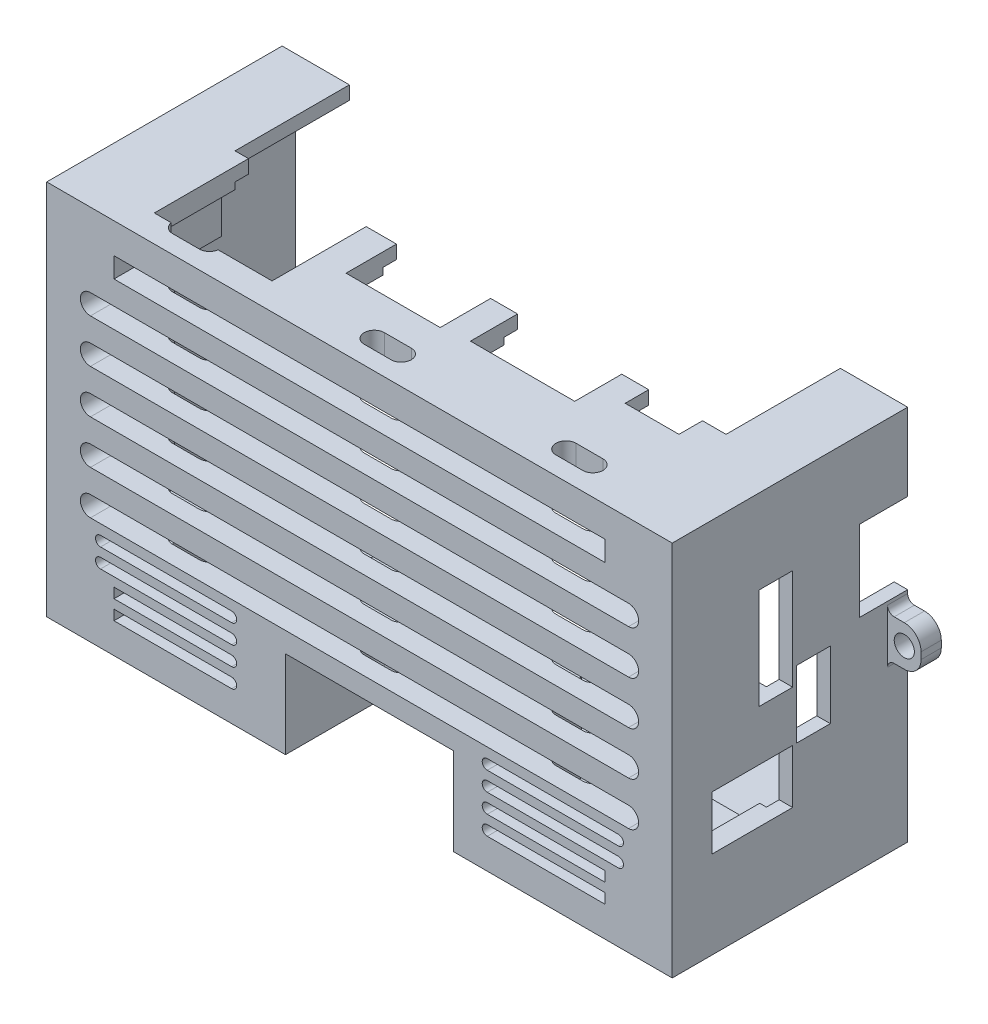
SolidWorks part; units mm, degrees
note: The reader was unsure of these and kept them because the rebuilt part matched: shared geometry of "草图3<3>", "草图3<5>", "草图3<7>".
ref_plane "前视基准面" through (0, 0, 0) normal (0, 0, 1) x (1, 0, 0)
ref_plane "上视基准面" through (0, 0, 0) normal (0, 1, 0) x (1, 0, 0)
ref_plane "右视基准面" through (0, 0, 0) normal (1, 0, 0) x (0, 0, -1)
sketch "草图1" plane through (0, 0, 0) normal (0, 0, 1) x (1, 0, 0)
  line L0 (-5, 0) -> (5, 0) construction
  line L1 (0, -5) -> (0, 5) construction
  line B0 (0, 28) -> (0, -28) construction
  line B1 (-46.5, 28) -> (46.5, 28)
  line B2 (-46.5, 28) -> (-46.5, -28)
  line B3 (-46.5, -28) -> (46.5, -28)
  line B4 (46.5, 28) -> (46.5, -28)
  line B5 (-46.5, 0) -> (46.5, 0) construction
  line B6 (-14.7618, 2.9185) -> (-17.7618, 2.9185) construction
  line B7 (0, 0) -> (-18, 0) construction
  line B8 (-14.0149, 5.8732) -> (-17.0149, 5.8732) construction
  line B9 (-12.6968, 8.8097) -> (-15.6968, 8.8097) construction
  line B10 (-10.6391, 11.7463) -> (-13.6391, 11.7463) construction
  line B11 (-7.4122, 14.6829) -> (-10.4122, 14.6829) construction
  line B12 (-15, 0) -> (-18, 0) construction
  line B13 (-20, 0) -> (20, 0) construction
  line B14 (-20, 20) -> (20, 20)
  line B15 (-20, 20) -> (-20, -20)
  line B16 (-20, -20) -> (20, -20)
  line B17 (20, 20) -> (20, -20)
  line B18 (0, 20) -> (0, -20) construction
  line B19 (-43.5, 25) -> (43.5, 25)
  line B20 (-43.5, 25) -> (-43.5, -25)
  line B21 (-43.5, -25) -> (43.5, -25)
  line B22 (43.5, 25) -> (43.5, -25)
  line B23 (-43.5, 0) -> (43.5, 0) construction
  line B24 (0, 25) -> (0, -25) construction
  line B25 (-39.5, 21) -> (-43.5, 21) construction
  line B26 (-39.5, 21) -> (-39.5, 25) construction
  line B27 (-39.5, -21) -> (39.5, -21) construction
  line B28 (39.5, -21) -> (39.5, 21) construction
  line B29 (39.5, 21) -> (43.5, 21) construction
  line B30 (39.5, 21) -> (39.5, 25) construction
  line B31 (-39.5, 21) -> (-39.5, -21) construction
  line B32 (39.5, 21) -> (-39.5, 21) construction
  line B33 (-39.5, -21) -> (-39.5, -25) construction
  line B34 (-39.5, -21) -> (-43.5, -21) construction
  line B35 (-23.25, 25) -> (-23.25, -25)
  line B36 (23.25, 25) -> (23.25, -25)
  line B37 (43.5, 17) -> (35.5, 17)
  line B38 (-43.5, 25) -> (-35.5, 25)
  line B39 (-43.5, 25) -> (-43.5, 17)
  line B40 (-43.5, 17) -> (-35.5, 17)
  line B41 (-35.5, 25) -> (-35.5, 17)
  line B42 (35.5, 25) -> (35.5, 17)
  line B43 (43.5, 25) -> (35.5, 25)
  line B44 (43.5, 25) -> (43.5, 17)
  line B45 (43.5, -25) -> (35.5, -25)
  line B46 (35.5, -25) -> (35.5, -17)
  line B47 (43.5, -17) -> (35.5, -17)
  line B48 (43.5, -25) -> (43.5, -17)
  line B49 (-43.5, -17) -> (-35.5, -17)
  line B50 (-35.5, -25) -> (-35.5, -17)
  line B51 (-43.5, -25) -> (-35.5, -25)
  line B52 (-43.5, -25) -> (-43.5, -17)
  line B53 (46.5, -18) -> (36.5, -18)
  line B54 (-46.5, -28) -> (-36.5, -28)
  line B55 (-46.5, -28) -> (-46.5, -18)
  line B56 (-46.5, -18) -> (-36.5, -18)
  line B57 (-36.5, -28) -> (-36.5, -18)
  line B58 (36.5, -28) -> (36.5, -18)
  line B59 (46.5, -28) -> (36.5, -28)
  line B60 (46.5, -28) -> (46.5, -18)
  line B61 (46.5, 28) -> (36.5, 28)
  line B62 (36.5, 28) -> (36.5, 18)
  line B63 (46.5, 18) -> (36.5, 18)
  line B64 (46.5, 28) -> (46.5, 18)
  line B65 (-46.5, 18) -> (-36.5, 18)
  line B66 (-36.5, 28) -> (-36.5, 18)
  line B67 (-46.5, 28) -> (-36.5, 28)
  line B68 (-46.5, 28) -> (-46.5, 18)
  circle B69 centre (0, 0) radius 18 construction
  circle B70 centre (-39.5, 21) radius 2
  circle B71 centre (39.5, 21) radius 2
  circle B72 centre (39.5, -21) radius 2
  circle B73 centre (-39.5, -21) radius 2
  circle B74 centre (0, 0) radius 18
  arc B75 (15, -1) -> (15, 1) centre (15, 0) ccw
  line B76 (-14.7618, 3.9185) -> (14.7618, 3.9185)
  line B77 (-12.6968, 9.8097) -> (12.6968, 9.8097)
  arc B78 (-10.6391, 12.7463) -> (-10.6391, 10.7463) centre (-10.6391, 11.7463) ccw
  line B79 (-10.6391, -12.7463) -> (10.6391, -12.7463)
  line B80 (-12.6968, -9.8097) -> (12.6968, -9.8097)
  line B81 (-12.6968, -7.8097) -> (12.6968, -7.8097)
  line B82 (-14.0149, -6.8732) -> (14.0149, -6.8732)
  line B83 (-14.0149, -4.8732) -> (14.0149, -4.8732)
  line B84 (-14.7594, -3.9185) -> (14.7642, -3.8479)
  line B85 (-14.7642, -1.9185) -> (14.7594, -1.8479)
  line B86 (-15, -1) -> (15, -1)
  line B87 (-15, 1) -> (15, 1)
  line B88 (-14.7618, 1.9185) -> (14.7618, 1.9185)
  line B89 (-14.0149, 4.8732) -> (14.0149, 4.8732)
  line B90 (-14.0149, 5.8732) -> (14.0149, 5.8732) construction
  line B91 (-14.7618, 2.9185) -> (14.7618, 2.9185) construction
  line B92 (-14.0149, 6.8732) -> (14.0149, 6.8732)
  line B93 (-12.6968, 8.8097) -> (12.6968, 8.8097) construction
  line B94 (-12.6968, 7.8097) -> (12.6968, 7.8097)
  line B95 (-10.6391, 11.7463) -> (10.6391, 11.7463) construction
  line B96 (-10.6391, 12.7463) -> (10.6391, 12.7463)
  line B97 (-10.6391, 10.7463) -> (10.6391, 10.7463)
  line B98 (-7.4122, 14.6829) -> (7.4122, 14.6829) construction
  line B99 (-7.4122, 15.6829) -> (7.4122, 15.6829)
  line B100 (-7.4122, 13.6829) -> (7.4122, 13.6829)
  line B101 (-14.7618, -2.9185) -> (14.7618, -2.8479) construction
  line B102 (-14.0149, -5.8732) -> (14.0149, -5.8732) construction
  line B103 (-12.6968, -8.8097) -> (12.6968, -8.8097) construction
  line B104 (-10.6391, -11.7463) -> (10.6391, -11.7463) construction
  line B105 (-10.6391, -10.7463) -> (10.6391, -10.7463)
  line B106 (-7.4122, -14.6829) -> (7.4122, -14.638) construction
  line B107 (-7.4091, -15.6829) -> (7.4152, -15.638)
  line B108 (-7.4152, -13.6829) -> (7.4091, -13.638)
  line B109 (-15, 0) -> (15, 0) construction
  arc B110 (-14.7618, 3.9185) -> (-14.7618, 1.9185) centre (-14.7618, 2.9185) ccw
  arc B111 (14.7618, 1.9185) -> (14.7618, 3.9185) centre (14.7618, 2.9185) ccw
  arc B112 (-14.0149, 6.8732) -> (-14.0149, 4.8732) centre (-14.0149, 5.8732) ccw
  arc B113 (14.0149, 4.8732) -> (14.0149, 6.8732) centre (14.0149, 5.8732) ccw
  arc B114 (-12.6968, 9.8097) -> (-12.6968, 7.8097) centre (-12.6968, 8.8097) ccw
  arc B115 (12.6968, 7.8097) -> (12.6968, 9.8097) centre (12.6968, 8.8097) ccw
  arc B116 (10.6391, 10.7463) -> (10.6391, 12.7463) centre (10.6391, 11.7463) ccw
  arc B117 (-7.4122, 15.6829) -> (-7.4122, 13.6829) centre (-7.4122, 14.6829) ccw
  arc B118 (7.4122, 13.6829) -> (7.4122, 15.6829) centre (7.4122, 14.6829) ccw
  arc B119 (-14.7594, -3.9185) -> (-14.7642, -1.9185) centre (-14.7618, -2.9185) cw
  arc B120 (14.7594, -1.8479) -> (14.7642, -3.8479) centre (14.7618, -2.8479) cw
  arc B121 (-14.0149, -6.8732) -> (-14.0149, -4.8732) centre (-14.0149, -5.8732) cw
  arc B122 (14.0149, -4.8732) -> (14.0149, -6.8732) centre (14.0149, -5.8732) cw
  arc B123 (-12.6968, -9.8097) -> (-12.6968, -7.8097) centre (-12.6968, -8.8097) cw
  arc B124 (12.6968, -7.8097) -> (12.6968, -9.8097) centre (12.6968, -8.8097) cw
  arc B125 (-10.6391, -12.7463) -> (-10.6391, -10.7463) centre (-10.6391, -11.7463) cw
  arc B126 (10.6391, -10.7463) -> (10.6391, -12.7463) centre (10.6391, -11.7463) cw
  arc B127 (-7.4091, -15.6829) -> (-7.4152, -13.6829) centre (-7.4122, -14.6829) cw
  arc B128 (7.4091, -13.638) -> (7.4152, -15.638) centre (7.4122, -14.638) cw
  arc B129 (-15, 1) -> (-15, -1) centre (-15, 0) ccw
  dimension "D1" = 10
  dimension "D2" = 10
sketch_block_instance "tx2_boxes_with_fan-1"
sketch_block "tx2_boxes_with_fan" parameters "D5"=36, "D7"=4, "D14"=36, "D1"=3, "D2"=3, "D3"=3, "D4"=2, "D6"=40, "D8"=79, "D9"=42, "D10"=50, "D11"=87, "D12"=4, "D13"=4, "D15"=23.25, "D16"=8, "D17"=8, "D18"=1, "D19"=1
extrude "凸台-拉伸1" add sketch "草图1" along normal blind 35 contours B65 B2 B56 B20 B39 | B3 B57 B21 B52 B56 B2 | B58 B3 B4 B53 B48 B45 | B4 B63 B44 B22 B53 | B3 B58 B21 B51 B57 | B66 B1 B2 B65 B20 B19 | B63 B4 B1 B62 B43 B22
sketch "草图2" plane through (0, 28, 0) normal (0, 1, 0) x (1, 0, 0)
  line L0 (0, -35) -> (0, 0) construction
  line L1 (-46.5, 0) -> (46.5, 0)
  line L2 (-46.5, 0) -> (-46.5, -35)
  line L3 (-46.5, -35) -> (46.5, -35)
  line L4 (46.5, 0) -> (46.5, -35)
  line L5 (-46.5, -17.5) -> (46.5, -17.5) construction
  line L6 (-46.5, -17) -> (46.5, -17)
  line L7 (-46.5, -15.5) -> (46.5, -15.5)
  line L9 (-34.5, -17) -> (-17, -17)
  line L10 (-34.5, -17) -> (-34.5, -31)
  line L11 (-34.5, -31) -> (-17, -31)
  line L12 (-17, -17) -> (-17, -31)
  line L14 (-12.5, -17) -> (1.5, -17)
  line L15 (-12.5, -17) -> (-12.5, -24.5)
  line L16 (-12.5, -24.5) -> (1.5, -24.5)
  line L17 (1.5, -17) -> (1.5, -24.5)
  line L19 (5.5, -17) -> (21, -17)
  line L20 (5.5, -17) -> (5.5, -24)
  line L21 (5.5, -24) -> (21, -24)
  line L22 (21, -17) -> (21, -24)
  line L24 (25, -17) -> (33, -17)
  line L25 (25, -17) -> (25, -20.5)
  line L26 (25, -20.5) -> (33, -20.5)
  line L27 (33, -17) -> (33, -20.5)
  line B0 (-43.5, -17) -> (43.5, -17)
  line B1 (-43.5, -15.5) -> (43.5, -15.5)
  line B2 (-34, -17) -> (-17.5, -17)
  line B3 (-34, -17) -> (-34, -30.5)
  line B4 (-34, -30.5) -> (-17.5, -30.5)
  line B5 (-17.5, -17) -> (-17.5, -30.5)
  line B6 (-12, -17) -> (1, -17)
  line B7 (-12, -17) -> (-12, -24)
  line B8 (-12, -24) -> (1, -24)
  line B9 (1, -17) -> (1, -24)
  line B10 (6, -17) -> (20.5, -17)
  line B11 (6, -17) -> (6, -23.5)
  line B12 (6, -23.5) -> (20.5, -23.5)
  line B13 (20.5, -17) -> (20.5, -23.5)
  line B14 (25.5, -17) -> (32.5, -17)
  line B15 (25.5, -17) -> (25.5, -20)
  line B16 (25.5, -20) -> (32.5, -20)
  line B17 (32.5, -17) -> (32.5, -20)
  line B18 (-43.5, -17) -> (43.5, -17)
  line B19 (-43.5, -17) -> (-43.5, -32.5)
  line B20 (-43.5, -32.5) -> (43.5, -32.5)
  line B21 (43.5, -17) -> (43.5, -32.5)
  line B22 (-43.5, -15.5) -> (-43.5, -17)
  line B23 (43.5, -15.5) -> (43.5, -17)
  line B24 (0, -17) -> (0, -32.5) construction
  line B25 (43.5, -24.75) -> (-43.5, -24.75) construction
  line M7 (36.5, -35) -> (46.5, -35)
  line M8 (46.5, -35) -> (46.5, 0)
  line M42 (36.5, 0) -> (36.5, -35)
  dimension "D1" = 35
  dimension "D2" = 93
  dimension "D3" = 17
  dimension "D4" = 1.5
  dimension "D5" = 18
  dimension "D6" = 0.5
  dimension "D7" = 0.5
  dimension "D8" = 0.5
  dimension "D9" = 0.5
  dimension "D10" = 0.5
  dimension "D11" = 0.5
  dimension "D12" = 0.5
  dimension "D13" = 0.5
  dimension "D14" = 0.5
  dimension "D15" = 0.5
  dimension "D16" = 0.5
  dimension "D17" = 0.5
sketch_block_instance "tx2_ethernet_usb_interface-1"
sketch_block "tx2_ethernet_usb_interface" parameters "D1"=16.5, "D2"=13.5, "D3"=5.5, "D4"=7, "D5"=13, "D6"=14.5, "D7"=6.5, "D8"=5, "D9"=7, "D10"=3, "D11"=5, "D12"=1.5, "D13"=15.5
sketch "草图3" plane through (0, 0, 35) normal (0, 0, 1) x (1, 0, 0)
  line L0 (1.5, -12) -> (1.5, -25) construction
  line L1 (-11, -15) -> (14, -15)
  line L2 (-11, -15) -> (-11, -25)
  line L3 (-11, -25) -> (14, -25)
  line L4 (14, -15) -> (14, -25)
  line L5 (-14, -12) -> (17, -12)
  line L6 (-14, -12) -> (-14, -25)
  line L7 (-14, -25) -> (17, -25)
  line L8 (17, -12) -> (17, -25)
  line L9 (-14, -25) -> (-14, -28)
  line L10 (-46.5, 28) -> (46.5, 28)
  line L11 (-46.5, 28) -> (-46.5, -28)
  line L12 (-46.5, -28) -> (46.5, -28)
  line L13 (46.5, 28) -> (46.5, -28)
  line L14 (17, -25) -> (17, -28)
  line L15 (-11, -25) -> (-11, -28)
  line L16 (0, 0) -> (-18, 0) construction
  line L17 (14, -25) -> (14, -28)
  line L21 (-15, 0) -> (-18, 0) construction
  line L22 (-20, 0) -> (20, 0) construction
  line L27 (0, 20) -> (0, -20) construction
  line L28 (-43.5, 25) -> (43.5, 25)
  line L29 (-43.5, 25) -> (-43.5, -25)
  line L30 (-43.5, -25) -> (43.5, -25)
  line L31 (43.5, 25) -> (43.5, -25)
  line L32 (-43.5, 0) -> (43.5, 0) construction
  line L33 (0, 25) -> (0, -25) construction
  line L34 (-39.5, 21) -> (-43.5, 21) construction
  line L35 (-39.5, 21) -> (-39.5, 25) construction
  line L36 (-39.5, -21) -> (39.5, -21) construction
  line L37 (39.5, -21) -> (39.5, 21) construction
  line L38 (39.5, 21) -> (43.5, 21) construction
  line L39 (39.5, 21) -> (39.5, 25) construction
  line L40 (-39.5, 21) -> (-39.5, -21) construction
  line L41 (39.5, 21) -> (-39.5, 21) construction
  line L42 (-39.5, -21) -> (-39.5, -25) construction
  line L43 (-39.5, -21) -> (-43.5, -21) construction
  line L45 (23.25, 25) -> (23.25, -25)
  line L46 (43.5, 17) -> (35.5, 17)
  line L47 (-43.5, 25) -> (-35.5, 25)
  line L48 (-43.5, 25) -> (-43.5, 17)
  line L49 (-43.5, 17) -> (-35.5, 17)
  line L50 (-35.5, 25) -> (-35.5, 17)
  line L51 (35.5, 25) -> (35.5, 17)
  line L52 (43.5, 25) -> (35.5, 25)
  line L53 (43.5, 25) -> (43.5, 17)
  line L54 (43.5, -25) -> (35.5, -25)
  line L55 (35.5, -25) -> (35.5, -17)
  line L56 (43.5, -17) -> (35.5, -17)
  line L57 (43.5, -25) -> (43.5, -17)
  line L58 (-43.5, -17) -> (-35.5, -17)
  line L59 (-35.5, -25) -> (-35.5, -17)
  line L60 (-43.5, -25) -> (-35.5, -25)
  line L61 (-43.5, -25) -> (-43.5, -17)
  line L62 (46.5, -18) -> (36.5, -18)
  line L63 (-46.5, -28) -> (-36.5, -28)
  line L64 (-46.5, -28) -> (-46.5, -18)
  line L65 (-46.5, -18) -> (-36.5, -18)
  line L66 (-36.5, -28) -> (-36.5, -18)
  line L67 (36.5, -28) -> (36.5, -18)
  line L68 (46.5, -28) -> (36.5, -28)
  line L69 (46.5, -28) -> (46.5, -18)
  line L70 (46.5, 28) -> (36.5, 28)
  line L71 (36.5, 28) -> (36.5, 18)
  line L72 (46.5, 18) -> (36.5, 18)
  line L73 (46.5, 28) -> (46.5, 18)
  line L74 (-46.5, 18) -> (-36.5, 18)
  line L75 (-36.5, 28) -> (-36.5, 18)
  line L76 (-46.5, 28) -> (-36.5, 28)
  line L77 (-46.5, 28) -> (-46.5, 18)
  circle A1 centre (-39.5, 21) radius 2
  circle A2 centre (39.5, 21) radius 2
  circle A3 centre (39.5, -21) radius 2
  circle A4 centre (-39.5, -21) radius 2
  line B0 (-39, 16) -> (-39, 15.5)
  line B1 (-41.5, 16) -> (-41, 16)
  line B2 (-41.5, 16) -> (-41.5, 15.5)
  line B3 (-41.5, 15.5) -> (-41, 15.5)
  line B4 (-41, 16) -> (-41, 15.5)
  line B5 (-43.5, 25) -> (43.5, 25)
  line B6 (-43.5, 25) -> (-43.5, -25)
  line B7 (-43.5, -25) -> (43.5, -25)
  line B8 (43.5, 25) -> (43.5, -25)
  line B9 (-39, 16) -> (-38.5, 16)
  line B10 (-38.5, 16) -> (-38.5, 15.5)
  line B11 (-39, 15.5) -> (-38.5, 15.5)
  line B12 (-41.5, 13.5) -> (-41.5, 13)
  line B13 (-41.5, 13.5) -> (-41, 13.5)
  line B14 (-41, 13.5) -> (-41, 13)
  line B15 (-41.5, 13) -> (-41, 13)
  line B16 (-39, 13.5) -> (-39, 13)
  line B17 (-39, 13.5) -> (-38.5, 13.5)
  line B18 (-38.5, 13.5) -> (-38.5, 13)
  line B19 (-39, 13) -> (-38.5, 13)
  line B20 (-41.5, 11) -> (-41.5, 10.5)
  line B21 (-41.5, 11) -> (-41, 11)
  line B22 (-41, 11) -> (-41, 10.5)
  line B23 (-41.5, 10.5) -> (-41, 10.5)
  line B24 (-39, 11) -> (-39, 10.5)
  line B25 (-39, 11) -> (-38.5, 11)
  line B26 (-38.5, 11) -> (-38.5, 10.5)
  line B27 (-39, 10.5) -> (-38.5, 10.5)
  line B28 (-41.5, 8.5) -> (-41.5, 8)
  line B29 (-41.5, 8.5) -> (-41, 8.5)
  line B30 (-41, 8.5) -> (-41, 8)
  line B31 (-41.5, 8) -> (-41, 8)
  line B32 (-39, 8.5) -> (-39, 8)
  line B33 (-39, 8.5) -> (-38.5, 8.5)
  line B34 (-38.5, 8.5) -> (-38.5, 8)
  line B35 (-39, 8) -> (-38.5, 8)
  line B36 (-41.5, 6) -> (-41.5, 5.5)
  line B37 (-41.5, 6) -> (-41, 6)
  line B38 (-41, 6) -> (-41, 5.5)
  line B39 (-41.5, 5.5) -> (-41, 5.5)
  line B40 (-39, 6) -> (-39, 5.5)
  line B41 (-39, 6) -> (-38.5, 6)
  line B42 (-38.5, 6) -> (-38.5, 5.5)
  line B43 (-39, 5.5) -> (-38.5, 5.5)
  line B44 (-41.5, 3.5) -> (-41.5, 3)
  line B45 (-41.5, 3.5) -> (-41, 3.5)
  line B46 (-41, 3.5) -> (-41, 3)
  line B47 (-41.5, 3) -> (-41, 3)
  line B48 (-39, 3.5) -> (-39, 3)
  line B49 (-39, 3.5) -> (-38.5, 3.5)
  line B50 (-38.5, 3.5) -> (-38.5, 3)
  line B51 (-39, 3) -> (-38.5, 3)
  line B52 (-41.5, 1) -> (-41.5, 0.5)
  line B53 (-41.5, 1) -> (-41, 1)
  line B54 (-41, 1) -> (-41, 0.5)
  line B55 (-41.5, 0.5) -> (-41, 0.5)
  line B56 (-39, 1) -> (-39, 0.5)
  line B57 (-39, 1) -> (-38.5, 1)
  line B58 (-38.5, 1) -> (-38.5, 0.5)
  line B59 (-39, 0.5) -> (-38.5, 0.5)
  line B60 (-41.5, -1.5) -> (-41.5, -2)
  line B61 (-41.5, -1.5) -> (-41, -1.5)
  line B62 (-41, -1.5) -> (-41, -2)
  line B63 (-41.5, -2) -> (-41, -2)
  line B64 (-39, -1.5) -> (-39, -2)
  line B65 (-39, -1.5) -> (-38.5, -1.5)
  line B66 (-38.5, -1.5) -> (-38.5, -2)
  line B67 (-39, -2) -> (-38.5, -2)
  line B68 (-41.5, -4) -> (-41.5, -4.5)
  line B69 (-41.5, -4) -> (-41, -4)
  line B70 (-41, -4) -> (-41, -4.5)
  line B71 (-41.5, -4.5) -> (-41, -4.5)
  line B72 (-39, -4) -> (-39, -4.5)
  line B73 (-39, -4) -> (-38.5, -4)
  line B74 (-38.5, -4) -> (-38.5, -4.5)
  line B75 (-39, -4.5) -> (-38.5, -4.5)
  line B76 (-41.5, -6.5) -> (-41.5, -7)
  line B77 (-41.5, -6.5) -> (-41, -6.5)
  line B78 (-41, -6.5) -> (-41, -7)
  line B79 (-41.5, -7) -> (-41, -7)
  line B80 (-39, -6.5) -> (-39, -7)
  line B81 (-39, -6.5) -> (-38.5, -6.5)
  line B82 (-38.5, -6.5) -> (-38.5, -7)
  line B83 (-39, -7) -> (-38.5, -7)
  line B84 (0, 25) -> (0, -25) construction
  line B85 (28.5, 15) -> (43.5, 15)
  line B86 (28.5, 15) -> (28.5, 1)
  line B87 (28.5, 1) -> (43.5, 1)
  line B88 (43.5, 15) -> (43.5, 1)
  line B89 (36, -7.5) -> (43.5, -7.5)
  line B90 (36, -7.5) -> (36, -14.5)
  line B91 (36, -14.5) -> (43.5, -14.5)
  line B92 (43.5, -7.5) -> (43.5, -14.5)
  line B93 (-43.5, 0) -> (43.5, 0) construction
  line B94 (-7.5, -22.25) -> (-5.5, -22.25) construction
  line B95 (-7.5, -21.5) -> (-5.5, -21.5)
  line B96 (-7.5, -23) -> (-5.5, -23)
  arc B97 (-7.5, -21.5) -> (-7.5, -23) centre (-7.5, -22.25) ccw
  arc B98 (-5.5, -23) -> (-5.5, -21.5) centre (-5.5, -22.25) ccw
  line B99 (1.5, -21) -> (1.5, -23.5) construction
  line B100 (-0.5, -21) -> (3.5, -21)
  line B101 (-0.5, -21) -> (-0.5, -23.5)
  line B102 (-0.5, -23.5) -> (3.5, -23.5)
  line B103 (3.5, -21) -> (3.5, -23.5)
  line B104 (-0.5, -22.25) -> (3.5, -22.25) construction
  line B105 (0.5, -22.25) -> (2.5, -22.25) construction
  line B106 (0.5, -21.5) -> (2.5, -21.5)
  line B107 (0.5, -23) -> (2.5, -23)
  arc B108 (0.5, -21.5) -> (0.5, -23) centre (0.5, -22.25) ccw
  arc B109 (2.5, -23) -> (2.5, -21.5) centre (2.5, -22.25) ccw
  line B110 (9.5, -21) -> (9.5, -23.5) construction
  line B111 (7.5, -21) -> (11.5, -21)
  line B112 (7.5, -21) -> (7.5, -23.5)
  line B113 (7.5, -23.5) -> (11.5, -23.5)
  line B114 (11.5, -21) -> (11.5, -23.5)
  line B115 (7.5, -22.25) -> (11.5, -22.25) construction
  line B116 (8.5, -22.25) -> (10.5, -22.25) construction
  line B117 (8.5, -21.5) -> (10.5, -21.5)
  line B118 (8.5, -23) -> (10.5, -23)
  arc B119 (8.5, -21.5) -> (8.5, -23) centre (8.5, -22.25) ccw
  arc B120 (10.5, -23) -> (10.5, -21.5) centre (10.5, -22.25) ccw
  line B121 (-6.5, -21) -> (-6.5, -23.5) construction
  line B122 (-8.5, -21) -> (-4.5, -21)
  line B123 (-8.5, -21) -> (-8.5, -23.5)
  line B124 (-8.5, -23.5) -> (-4.5, -23.5)
  line B125 (-4.5, -21) -> (-4.5, -23.5)
  line B126 (-8.5, -22.25) -> (-4.5, -22.25) construction
  line B127 (-7.5, -22.25) -> (-5.5, -22.25) construction
  line B128 (-7.5, -21.5) -> (-5.5, -21.5)
  line B129 (-7.5, -23) -> (-5.5, -23)
  arc B130 (-7.5, -21.5) -> (-7.5, -23) centre (-7.5, -22.25) ccw
  arc B131 (-5.5, -23) -> (-5.5, -21.5) centre (-5.5, -22.25) ccw
  line M4 (43.5, 25) -> (43.5, -25)
  line M5 (43.5, -25) -> (-43.5, -25)
  line M6 (-43.5, -25) -> (-43.5, 25)
  line M7 (36.5, 25) -> (43.5, 25)
  line M8 (-46.5, -28) -> (46.5, -28)
  line M9 (46.5, -28) -> (46.5, 28)
  line M10 (46.5, 28) -> (36.5, 28)
  line M11 (-46.5, 28) -> (-46.5, -28)
  line M272 (-46.5, -28) -> (46.5, -28)
  line M274 (43.5, -25) -> (-43.5, -25)
  line M275 (-43.5, 25) -> (-36.5, 25)
  line M276 (-36.5, 25) -> (-36.5, 28)
  line M277 (-36.5, 28) -> (-46.5, 28)
  dimension "D11" = 4
  dimension "D1" = 3
  dimension "D2" = 3
  dimension "D3" = 25
  dimension "D4" = 10
  dimension "D5" = 3
  dimension "D6" = 3
  dimension "D12" = 79
  dimension "D13" = 42
  dimension "D14" = 50
  dimension "D15" = 87
  dimension "D16" = 4
  dimension "D17" = 4
  dimension "D20" = 8
  dimension "D21" = 8
  dimension "D22" = 1
  dimension "D23" = 1
sketch_block_instance "tx2_key_and_sd_card-3"
sketch_block "tx2_key_and_sd_card" parameters "D1"=0.5, "D2"=0.5, "D3"=2, "D4"=9, "D5"=2.5, "D6"=2.5, "D7"=15, "D8"=14, "D9"=10, "D10"=7.5, "D11"=7, "D12"=10.5, "D13"=87, "D14"=50
sketch_block_instance "button-8"
sketch_block "button" parameters "D1"=4, "D2"=2.5
sketch_block_instance "button-9"
sketch_block_instance "button-1"
extrude "切除-拉伸1" cut sketch "草图3" against normal blind 18 contours L75 L74 L48 M10 M11 M7 | L75 L48 L74 A1 M7 | L47 L75 L74 L29 L49 L50 | A1 | L66 L60 L65 L11 M8 M6 | L60 L66 L65 A4 M6 | A4 | L66 L59 L58 L61 L65 M5 | L67 L57 L62 A3 M5 | L54 L67 L62 L56 L55 M4 | L67 L62 L57 M8 M9 M5 | L72 L71 L52 M9 M10 M4 | L72 L52 L71 A2 M4 | A2 | L53 L72 L71 L28 L51 L46 | L10 L75 L47 L28 L71 M7
extrude "凸台-拉伸2" add sketch "草图3<3>" against normal blind 18 contours L75 L48 L74 A1 M275 | L60 L66 L65 A4 M6 | L67 L57 L62 A3 M274 | L72 L71 A2 M4 M7 | L66 L60 L65 L11 M272 M6 | L67 L62 L57 M272 M9 M274 | L13 L72 L53 L31 B8 L62 M4 | L74 L48 M11 M275 M276 M277 | L8 L5 L6 L2 L1 L4 M274
sketch "草图3<3>" plane through (0, 0, 35) normal (0, 0, 1) x (1, 0, 0) same geometry as "草图3"
extrude "凸台-拉伸3" add sketch "草图2" against normal blind 3 contours B20 B19 L6 L2 L3 M42 | B19 B20 L6 L27 L26 L25 L22 L21 L20 L17 L16 L15 L12 L11 L10 M42 | L6 B21 B20 M42 M7 M8 | B21 L6 B20 M42 | B23 L7 L6 M42 | L7 B23 L6 L4 | B22 L7 L2 L6
sketch "草图4" plane through (46.5, 0, 0) normal (1, 0, 0) x (0, 0, -1)
  line L0 (-35, 0) -> (0, 0) construction
  line L1 (-35, 28) -> (0, 28)
  line L2 (-35, 28) -> (-35, -28)
  line L3 (-35, -28) -> (0, -28)
  line L4 (0, 28) -> (0, -28)
  line L5 (-17.5, 28) -> (-17.5, -28) construction
  line L6 (-17, 28) -> (-17, -28)
  line L7 (-15.5, 28) -> (-15.5, -28)
  line L8 (-17.1, 8) -> (-22.1, 8) construction
  line L9 (-17.1, 15.5) -> (-22.1, 15.5)
  line L10 (-17.1, 15.5) -> (-17.1, 0.5)
  line L11 (-17.1, 0.5) -> (-22.1, 0.5)
  line L12 (-22.1, 15.5) -> (-22.1, 0.5)
  line L13 (-17.1, -11) -> (-29.1, -11) construction
  line L14 (-17.1, -7) -> (-29.1, -7)
  line L15 (-17.1, -7) -> (-17.1, -15)
  line L16 (-17.1, -15) -> (-29.1, -15)
  line L17 (-29.1, -7) -> (-29.1, -15)
  line L18 (-11.5, -2) -> (-16.5, -2) construction
  line L19 (-11.5, 3) -> (-16.5, 3)
  line L20 (-11.5, 3) -> (-11.5, -7)
  line L21 (-11.5, -7) -> (-16.5, -7)
  line L22 (-16.5, 3) -> (-16.5, -7)
  line L23 (0, 25) -> (-35, 25)
  line L24 (0, -25) -> (-35, -25)
  line L26 (-7.1806, 16.5) -> (0, 16.5)
  line L27 (-7.1806, 16.5) -> (-7.1806, 4.5)
  line L28 (-7.1806, 4.5) -> (0, 4.5)
  line L29 (0, 16.5) -> (0, 4.5)
  dimension "D1" = 17
  dimension "D2" = 1.5
  dimension "D3" = 15
  dimension "D4" = 5
  dimension "D5" = 8
  dimension "D6" = 12
  dimension "D7" = 14
  dimension "D8" = 17
  dimension "D9" = 0.1
  dimension "D10" = 0.1
  dimension "D11" = 10
  dimension "D12" = 5
  dimension "D13" = 27
  dimension "D14" = 1
  dimension "D15" = 25
  dimension "D16" = 25
  dimension "D17" = 12
  dimension "D18" = 1
extrude "切除-拉伸2" cut sketch "草图4" against normal blind 3 contours L9 L12 L11 L10 | L21 L20 L19 L7 | L14 L17 L16 L15 | L19 L22 L21 L7 | L27 L26 L29 L28
extrude "切除-拉伸3" cut sketch "草图3<5>" along normal blind 2 from surface at -18 contours L75 L48 L74 A1 M275 | L60 L66 L65 A4 M6 | L67 L57 L62 A3 M274 | L72 L71 A2 M4 M7 starting at face at (-40, -21.5, 17)
sketch "草图3<5>" plane through (0, 0, 35) normal (0, 0, 1) x (1, 0, 0) same geometry as "草图3"
sketch "草图5" plane through (0, 0, 35) normal (0, 0, 1) x (1, 0, 0)
  line L1 (-46.5, 28) -> (46.5, 28)
  line L2 (-46.5, 28) -> (-46.5, -28)
  line L3 (-46.5, -28) -> (46.5, -28)
  line L4 (46.5, 28) -> (46.5, -28)
extrude "凸台-拉伸4" add sketch "草图5" against normal blind 3
extrude "切除-拉伸4" cut sketch "草图3<7>" against normal blind 18 contours L17 L15 L12 M274 | L4 L1 L2 B111 B114 B113 B112 B100 B103 B102 B101 B122 B125 B124 B123 M274 | B125 B122 B123 B124 B98 B96 B97 B95 | B96 B98 B95 B97 | B103 B100 B101 B102 B109 B107 B108 B106 | B107 B109 B106 B108 | B114 B111 B112 B113 B120 B118 B119 B117 | B118 B120 B117 B119
sketch "草图3<7>" plane through (0, 0, 35) normal (0, 0, 1) x (1, 0, 0) same geometry as "草图3"
sketch "草图6" plane through (0, 0, 35) normal (0, 0, 1) x (1, 0, 0)
  line L0 (0, 25) -> (0, -25) construction
  line L1 (-43.5, 25) -> (43.5, 25)
  line L2 (-43.5, 25) -> (-43.5, -25)
  line L3 (-43.5, -25) -> (43.5, -25)
  line L4 (43.5, 25) -> (43.5, -25)
  line L5 (-46.5, 28) -> (46.5, 28)
  line L6 (-46.5, 28) -> (-46.5, -28)
  line L7 (-46.5, -28) -> (46.5, -28)
  line L8 (46.5, 28) -> (46.5, -28)
  line L9 (-40, 22) -> (40, 22) construction
  line L10 (-40, 23.5) -> (40, 23.5)
  line L11 (-40, 20.5) -> (40, 20.5)
  line L12 (-40, 15.5) -> (40, 15.5) construction
  line L13 (-40, 17) -> (40, 17)
  line L14 (-40, 14) -> (40, 14)
  line L15 (-40, 9) -> (40, 9) construction
  line L16 (-40, 10.5) -> (40, 10.5)
  line L17 (-40, 7.5) -> (40, 7.5)
  line L18 (-40, 2.5) -> (40, 2.5) construction
  line L19 (-40, 4) -> (40, 4)
  line L20 (-40, 1) -> (40, 1)
  line L21 (-40, -4) -> (40, -4) construction
  line L22 (-40, -2.5) -> (40, -2.5)
  line L23 (-40, -5.5) -> (40, -5.5)
  line L24 (-40, -10.5) -> (40, -10.5) construction
  line L25 (-40, -9) -> (40, -9)
  line L26 (-40, -12) -> (40, -12)
  line L27 (-11, -15) -> (14, -15) construction
  line L28 (14, -21.5) -> (43.5, -21.5) construction
  line L29 (14, -15) -> (14, -28) construction
  line L30 (28.75, -21.5) -> (28.75, 25) construction
  line L31 (19, -14.25) -> (38.5, -14.25) construction
  line L32 (19, -13.5) -> (38.5, -13.5)
  line L33 (19, -15) -> (38.5, -15)
  line L34 (19, -17.0833) -> (38.5, -17.0833) construction
  line L35 (19, -16.3333) -> (38.5, -16.3333)
  line L36 (19, -17.8333) -> (38.5, -17.8333)
  line L37 (19, -19.9167) -> (38.5, -19.9167) construction
  line L38 (19, -19.1667) -> (38.5, -19.1667)
  line L39 (19, -20.6667) -> (38.5, -20.6667)
  line L40 (19, -22.75) -> (38.5, -22.75) construction
  line L41 (19, -22) -> (38.5, -22)
  line L42 (19, -23.5) -> (38.5, -23.5)
  line L43 (-19, -22.75) -> (-38.5, -22.75) construction
  line L44 (-19, -22) -> (-38.5, -22)
  line L45 (-19, -23.5) -> (-38.5, -23.5)
  line L46 (-19, -19.9167) -> (-38.5, -19.9167) construction
  line L47 (-19, -19.1667) -> (-38.5, -19.1667)
  line L48 (-19, -20.6667) -> (-38.5, -20.6667)
  line L49 (-19, -17.0833) -> (-38.5, -17.0833) construction
  line L50 (-19, -16.3333) -> (-38.5, -16.3333)
  line L51 (-19, -17.8333) -> (-38.5, -17.8333)
  line L52 (-19, -14.25) -> (-38.5, -14.25) construction
  line L53 (-19, -13.5) -> (-38.5, -13.5)
  line L54 (-19, -15) -> (-38.5, -15)
  line L55 (43.5, -25) -> (36.5, -25)
  line L56 (-43.5, -18) -> (-36.5, -18)
  line L57 (-43.5, -18) -> (-43.5, -25)
  line L58 (-43.5, -25) -> (-36.5, -25)
  line L59 (-36.5, -18) -> (-36.5, -25)
  line L60 (36.5, -18) -> (36.5, -25)
  line L61 (43.5, -18) -> (36.5, -18)
  line L62 (43.5, -18) -> (43.5, -25)
  line L63 (-43.5, 0) -> (43.5, 0) construction
  line L64 (-43.5, 25) -> (-36.5, 25)
  line L65 (-36.5, 18) -> (-36.5, 25)
  line L66 (-43.5, 18) -> (-36.5, 18)
  line L67 (-43.5, 18) -> (-43.5, 25)
  line L68 (43.5, 18) -> (43.5, 25)
  line L69 (43.5, 18) -> (36.5, 18)
  line L70 (36.5, 18) -> (36.5, 25)
  line L71 (43.5, 25) -> (36.5, 25)
  arc A0 (-40, 23.5) -> (-40, 20.5) centre (-40, 22) ccw
  arc A1 (40, 20.5) -> (40, 23.5) centre (40, 22) ccw
  arc A2 (-40, 17) -> (-40, 14) centre (-40, 15.5) ccw
  arc A3 (40, 14) -> (40, 17) centre (40, 15.5) ccw
  arc A4 (-40, 10.5) -> (-40, 7.5) centre (-40, 9) ccw
  arc A5 (40, 7.5) -> (40, 10.5) centre (40, 9) ccw
  arc A6 (-40, 4) -> (-40, 1) centre (-40, 2.5) ccw
  arc A7 (40, 1) -> (40, 4) centre (40, 2.5) ccw
  arc A8 (-40, -2.5) -> (-40, -5.5) centre (-40, -4) ccw
  arc A9 (40, -5.5) -> (40, -2.5) centre (40, -4) ccw
  arc A10 (-40, -9) -> (-40, -12) centre (-40, -10.5) ccw
  arc A11 (40, -12) -> (40, -9) centre (40, -10.5) ccw
  arc A12 (19, -13.5) -> (19, -15) centre (19, -14.25) ccw
  arc A13 (38.5, -15) -> (38.5, -13.5) centre (38.5, -14.25) ccw
  arc A14 (19, -16.3333) -> (19, -17.8333) centre (19, -17.0833) ccw
  arc A15 (38.5, -17.8333) -> (38.5, -16.3333) centre (38.5, -17.0833) ccw
  arc A16 (19, -19.1667) -> (19, -20.6667) centre (19, -19.9167) ccw
  arc A17 (38.5, -20.6667) -> (38.5, -19.1667) centre (38.5, -19.9167) ccw
  arc A18 (19, -22) -> (19, -23.5) centre (19, -22.75) ccw
  arc A19 (38.5, -23.5) -> (38.5, -22) centre (38.5, -22.75) ccw
  arc A20 (-19, -22) -> (-19, -23.5) centre (-19, -22.75) cw
  arc A21 (-38.5, -23.5) -> (-38.5, -22) centre (-38.5, -22.75) cw
  arc A22 (-19, -19.1667) -> (-19, -20.6667) centre (-19, -19.9167) cw
  arc A23 (-38.5, -20.6667) -> (-38.5, -19.1667) centre (-38.5, -19.9167) cw
  arc A24 (-19, -16.3333) -> (-19, -17.8333) centre (-19, -17.0833) cw
  arc A25 (-38.5, -17.8333) -> (-38.5, -16.3333) centre (-38.5, -17.0833) cw
  arc A26 (-19, -13.5) -> (-19, -15) centre (-19, -14.25) cw
  arc A27 (-38.5, -15) -> (-38.5, -13.5) centre (-38.5, -14.25) cw
  point P14 (0, 22)
  point P23 (0, 15.5)
  point P30 (0, 9)
  point P37 (0, 2.5)
  point P44 (0, -4)
  point P51 (0, -10.5)
  point P66 (28.75, -14.25)
  point P74 (28.75, -17.0833)
  point P81 (28.75, -19.9167)
  point P88 (28.75, -22.75)
  point P94 (-28.75, -22.75)
  point P101 (-28.75, -19.9167)
  point P108 (-28.75, -17.0833)
  point P115 (-28.75, -14.25)
  dimension "D1" = 3
  dimension "D2" = 3
  dimension "D3" = 80
  dimension "D4" = 3
  dimension "D5" = 3
  dimension "D7" = 3
  dimension "D8" = 5
  dimension "D9" = 1.5
  dimension "D10" = 1.5
  dimension "D12" = 1.5
  dimension "D13" = 7
  dimension "D14" = 7
  dimension "D6" = 6
  dimension "D11" = 4
extrude "切除-拉伸5" cut sketch "草图6" against normal blind 3 contours L11 A1 L10 A0 | L14 A3 L13 A2 | L17 A5 L16 A4 | L20 A7 L19 A6 | L23 A9 L22 A8 | L26 A11 L25 A10 | A27 L54 A26 L53 | A25 L51 A24 L50 | A21 L45 A20 L44 | A23 L48 A22 L47 | L42 A19 L41 A18 | L39 A17 L38 A16 | L36 A15 L35 A14 | L33 A13 L32 A12
sketch "草图8" plane through (0, 0, 0) normal (0, 0, -1) x (-1, 0, 0)
  line L0 (0, 28) -> (0, -28) construction
  line L1 (-46.5, 28) -> (46.5, 28)
  line L2 (-46.5, 28) -> (-46.5, -28)
  line L3 (-46.5, -28) -> (46.5, -28)
  line L4 (46.5, 28) -> (46.5, -28)
  line B0 (-51.5, 0) -> (-46.5, 0) construction
  line B1 (-51.5, -0.5) -> (-51.5, 0.5)
  line B2 (-49, -3) -> (-47.899, -3)
  line B3 (-49, 3) -> (-47.899, 3)
  line B4 (-47.899, -3) -> (-47.5, -3)
  line B5 (-46.5, -3) -> (-46.5, 3)
  line B6 (-47.5, 3) -> (-47.899, 3)
  line B7 (-46.5, 4) -> (-46.5, -4)
  circle B8 centre (-49, 0) radius 1.5
  arc B9 (-49, 3) -> (-51.5, 0.5) centre (-49, 0.5) ccw
  arc B10 (-51.5, -0.5) -> (-49, -3) centre (-49, -0.5) ccw
  arc B11 (-46.5, -4) -> (-47.5, -3) centre (-47.5, -4) ccw
  arc B12 (-47.5, 3) -> (-46.5, 4) centre (-47.5, 4) ccw
  line B13 (51.5, 0) -> (46.5, 0) construction
  line B14 (51.5, -0.5) -> (51.5, 0.5)
  line B15 (49, -3) -> (47.899, -3)
  line B16 (49, 3) -> (47.899, 3)
  line B17 (47.899, -3) -> (47.5, -3)
  line B18 (46.5, -3) -> (46.5, 3)
  line B19 (47.5, 3) -> (47.899, 3)
  line B20 (46.5, 4) -> (46.5, -4)
  circle B21 centre (49, 0) radius 1.5
  arc B22 (49, 3) -> (51.5, 0.5) centre (49, 0.5) cw
  arc B23 (51.5, -0.5) -> (49, -3) centre (49, -0.5) cw
  arc B24 (46.5, -4) -> (47.5, -3) centre (47.5, -4) cw
  arc B25 (47.5, 3) -> (46.5, 4) centre (47.5, 4) cw
sketch_block_instance "ear_3mm-1"
sketch_block "ear_3mm" parameters "D1"=3, "D2"=2.5, "D4"=1, "D5"=1, "D3"=2.5
sketch_block_instance "ear_3mm-3"
extrude "凸台-拉伸5" add sketch "草图8" against normal blind 3
sketch "草图9" plane through (0, 0, 0) normal (0, 0, -1) x (-1, 0, 0)
  line L1 (-44.5, 26) -> (44.5, 26)
  line L2 (-44.5, 26) -> (-44.5, -26)
  line L3 (-44.5, -26) -> (44.5, -26)
  line L4 (44.5, 26) -> (44.5, -26)
  line L5 (43.5, -25) -> (-43.5, -25)
  line L6 (43.5, -25) -> (43.5, 25)
  line L7 (43.5, 25) -> (-43.5, 25)
  line L8 (-43.5, -25) -> (-43.5, 25)
  dimension "D1" = 1
  dimension "D2" = 1
  dimension "D3" = 1
  dimension "D4" = 1
extrude "切除-拉伸6" cut sketch "草图9" against normal up to surface (19 mm away) contours L2 L1 L4 L3
sketch "草图10" plane through (0, 28, 0) normal (0, 1, 0) x (1, 0, 0)
  line L0 (26.5, -30.7999) -> (30.5, -30.7999) construction
  line L1 (26.5, -29.2999) -> (30.5, -29.2999)
  line L2 (26.5, -32.2999) -> (30.5, -32.2999)
  line L3 (-2, -30.7999) -> (2, -30.7999) construction
  line L4 (-2, -29.2999) -> (2, -29.2999)
  line L5 (-2, -32.2999) -> (2, -32.2999)
  line L6 (-30.5, -30.7999) -> (-26.5, -30.7999) construction
  line L7 (-30.5, -29.2999) -> (-26.5, -29.2999)
  line L8 (-30.5, -32.2999) -> (-26.5, -32.2999)
  line L10 (0, 0) -> (0, -35) construction
  line L11 (-46.5, 0) -> (46.5, 0)
  line L12 (-46.5, 0) -> (-46.5, -35)
  line L13 (-46.5, -35) -> (46.5, -35)
  line L14 (46.5, 0) -> (46.5, -35)
  arc A0 (26.5, -29.2999) -> (26.5, -32.2999) centre (26.5, -30.7999) ccw
  arc A1 (30.5, -32.2999) -> (30.5, -29.2999) centre (30.5, -30.7999) ccw
  arc A2 (-2, -29.2999) -> (-2, -32.2999) centre (-2, -30.7999) ccw
  arc A3 (2, -32.2999) -> (2, -29.2999) centre (2, -30.7999) ccw
  arc A4 (-30.5, -29.2999) -> (-30.5, -32.2999) centre (-30.5, -30.7999) ccw
  arc A5 (-26.5, -32.2999) -> (-26.5, -29.2999) centre (-26.5, -30.7999) ccw
  point P2 (28.5, -30.7999)
  point P10 (0, -30.7999)
  point P17 (-28.5, -30.7999)
  line M22 (-17, -31) -> (-34.5, -31)
  dimension "D1" = 3
  dimension "D2" = 18
  dimension "D3" = 4
  dimension "D4" = 18
  dimension "D5" = 3
extrude "切除-拉伸7" cut sketch "草图10" against normal through all contours L8 A5 L7 A4 | L5 A3 L4 A2 | L2 A1 L1 A0 | L8 A5 A4 M22
sketch "草图11" plane through (-46.5, 0, 0) normal (-1, 0, 0) x (0, 0, 1)
  line L0 (0, 28) -> (0, 4) construction
  line L1 (25, 17) -> (29, 17)
  line L2 (25, 17) -> (25, -8)
  line L3 (25, -8) -> (29, -8)
  line L4 (29, 17) -> (29, -8)
  line L5 (35, 28) -> (35, -28) construction
  line L6 (35, 0) -> (0, 0) construction
  line L7 (0, 28) -> (35, 28) construction
  dimension "D1" = 25
  dimension "D2" = 25
  dimension "D3" = 11
  dimension "D4" = 4
extrude "切除-拉伸8" cut sketch "草图11" against normal blind 6 contours L2 L1 L4 L3
